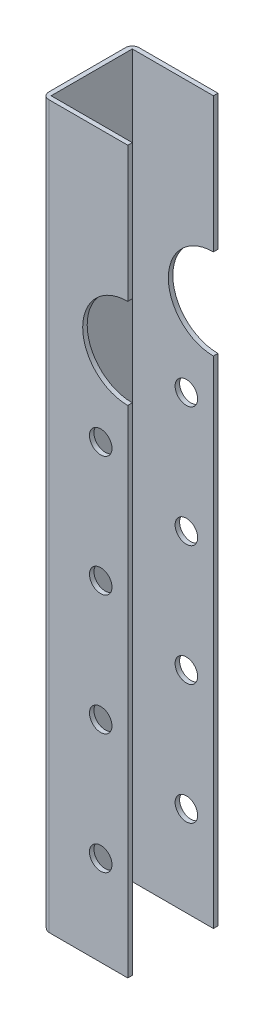
SolidWorks part; units mm, degrees
ref_plane "Front Plane" through (0, 0, 0) normal (0, 0, 1) x (1, 0, 0)
ref_plane "Top Plane" through (0, 0, 0) normal (0, 1, 0) x (1, 0, 0)
ref_plane "Right Plane" through (0, 0, 0) normal (1, 0, 0) x (0, 0, -1)
sketch "Sketch1" plane through (0, 0, 0) normal (0, 1, 0) x (1, 0, 0)
  line L1 (-12.7, -12.7) -> (12.7, -12.7)
  line L2 (-12.7, -12.7) -> (-12.7, 12.7)
  line L3 (-12.7, 12.7) -> (12.7, 12.7)
  line L4 (12.7, -12.7) -> (12.7, 12.7)
  line L5 (-12.7, -12.7) -> (12.7, 12.7) construction
  line L6 (-12.7, 12.7) -> (12.7, -12.7) construction
  line L7 (-11.43, -11.43) -> (11.43, -11.43)
  line L8 (-11.43, -11.43) -> (-11.43, 11.43)
  line L9 (-11.43, 11.43) -> (11.43, 11.43)
  line L10 (11.43, -11.43) -> (11.43, 11.43)
  line L11 (-11.43, -11.43) -> (11.43, 11.43) construction
  line L12 (-11.43, 11.43) -> (11.43, -11.43) construction
  point P0 (0, 0)
  point P6 (0, 0)
  dimension "D2" = 25.4
  dimension "D3" = 22.86
extrude "Boss-Extrude1" add sketch "Sketch1" along normal blind 203.2
sketch "Sketch2" plane through (12.7, 0, 0) normal (1, 0, 0) x (0, 0, -1)
  line L1 (-12.7, 203.2) -> (12.7, 203.2)
  line L2 (-12.7, 203.2) -> (-12.7, 0)
  line L3 (-12.7, 0) -> (12.7, 0)
  line L4 (12.7, 203.2) -> (12.7, 0)
extrude "Cut-Extrude1" cut sketch "Sketch2" against normal up to surface (1.27 mm away) up to face at (11.43, 101.6, 0)
sketch "Sketch4" plane through (0, 0, 12.7) normal (0, 0, 1) x (1, 0, 0)
  line L1 (11.43, 203.2) -> (11.43, 0) construction
  line L2 (-12.7, 203.2) -> (11.43, 203.2) construction
  arc A1 (11.43, 165.1) -> (11.43, 139.7) centre (11.43, 152.4) ccw
  dimension "D1" = 12.7
  dimension "D2" = 50.8
extrude "Cut-Extrude3" cut sketch "Sketch4" against normal through all both and the other way through all
fillet "Fillet10" radius 1.905 3 edges at (-12.7, 101.6, -12.7) (-12.7, 101.6, 12.7) (-12.7, 0, 0)
sketch "Sketch5" plane through (0, 0, 12.7) normal (0, 0, 1) x (1, 0, 0)
  line L0 (-10.795, 0) -> (11.43, 0) construction
  line L1 (11.43, 139.7) -> (11.43, 0) construction
  circle A0 centre (3.81, 25.4) radius 3.175
  circle A1 centre (3.81, 59.2667) radius 3.175
  circle A2 centre (3.81, 93.1333) radius 3.175
  circle A3 centre (3.81, 127) radius 3.175
  arc A4 (11.43, 165.1) -> (11.43, 139.7) centre (11.43, 152.4) ccw construction
  point P5 (0.3175, 0)
  point P14 (4.5507, 25.4)
  dimension "D2" = 25.4
  dimension "D1" = 6.35
  dimension "D4" = 25.4
  dimension "D5" = 7.62
  dimension "D3" = 4
extrude "Cut-Extrude4" cut sketch "Sketch5" against normal through all
equation "\"mount_length\"= 8"
equation "\"mount_height\"= 1"
equation "\"mount_width\"= 1"
equation "\"D1@Sketch1\"=\"mount_height\""
equation "\"D2@Sketch1\"=\"mount_width\""
equation "\"D3@Sketch1\"=\"mount_width\"-.1"
equation "\"D1@Boss-Extrude1\"=\"mount_length\""
equation "\"edge_dist\"= 1"
equation "\"hose_rad\"= .5"
equation "\"D1@Sketch4\"=\"hose_rad\""
equation "\"D2@Sketch5\"=\"edge_dist\""
equation "\"D4@Sketch5\"=\"edge_dist\""
